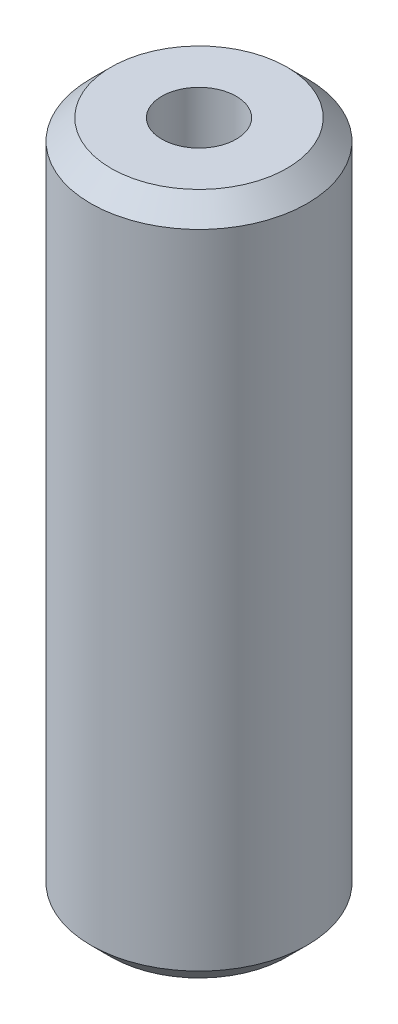
SolidWorks part; units mm, degrees
ref_plane "Front Plane" through (0, 0, 0) normal (0, 0, 1) x (1, 0, 0)
ref_plane "Top Plane" through (0, 0, 0) normal (0, 1, 0) x (1, 0, 0)
ref_plane "Right Plane" through (0, 0, 0) normal (1, 0, 0) x (0, 0, -1)
sketch "Sketch1" plane through (0, 0, 0) normal (0, 1, 0) x (1, 0, 0)
  circle A0 centre (0, 0) radius 15
  dimension "SHAFT_OD" = 30
extrude "Boss-Extrude1" add sketch "Sketch1" along normal blind 94.7058
sketch "Sketch2" plane through (0, 0, 0) normal (0, 1, 0) x (1, 0, 0)
  circle A0 centre (0, 0) radius 5.1646
  dimension "BORE_D" = 10.3291
extrude "Cut-Extrude1" cut sketch "Sketch2" along normal through all
chamfer "Chamfer1" distance 2.8151 angle 45 2 edges at (0, 94.7058, 15) (0, 0, 15)
